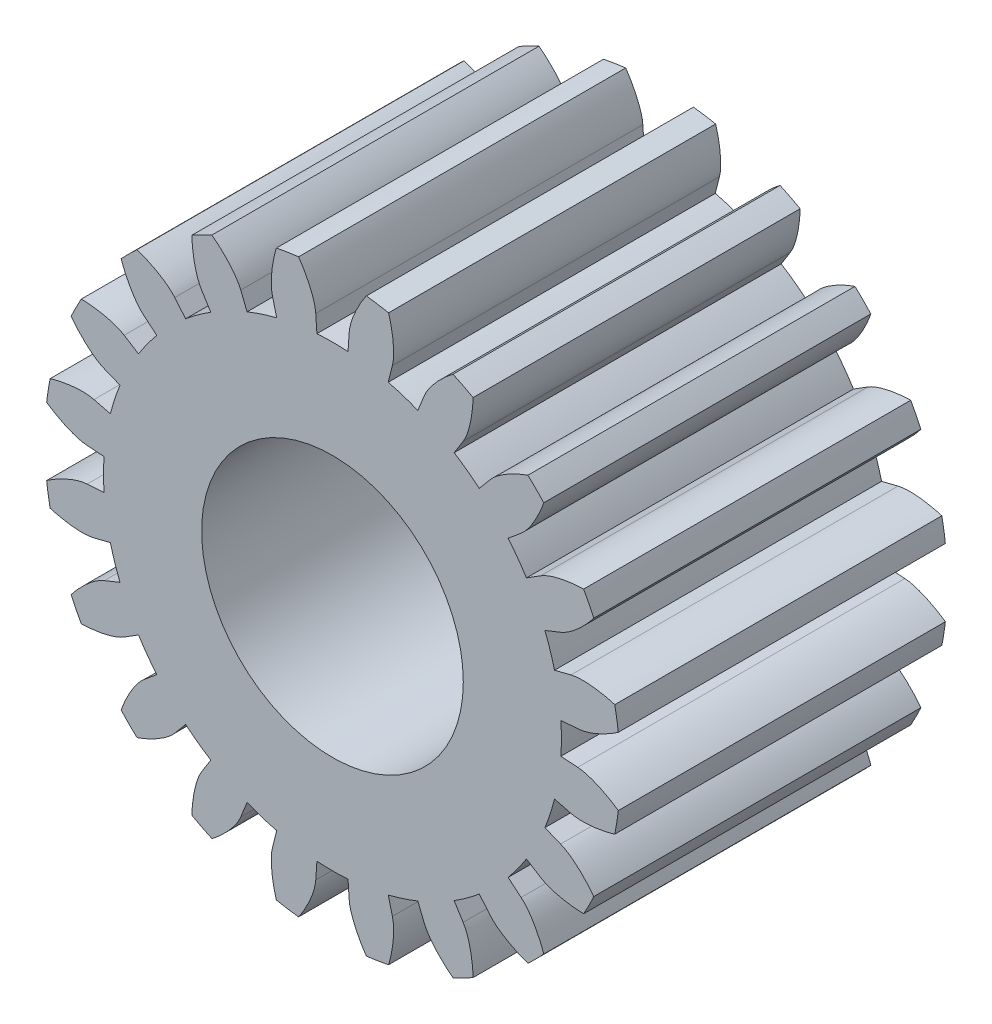
SolidWorks part; units mm, degrees
ref_plane "前视基准面" through (0, 0, 0) normal (0, 0, 1) x (1, 0, 0)
ref_plane "上视基准面" through (0, 0, 0) normal (0, 1, 0) x (1, 0, 0)
ref_plane "右视基准面" through (0, 0, 0) normal (1, 0, 0) x (0, 0, -1)
other "Configuration Table"
sketch "草图1" plane through (0, 0, 0) normal (0, 0, 1) x (1, 0, 0)
  line L0 (0, 0) -> (2, 0) construction
  line L1 (0, 0) -> (1.9938, 0.1569) construction
  line L2 (0, 0) -> (1.875, 0.1277)
  line L3 (1.9938, 0.1569) -> (1.9938, -0.1569) construction
  line L4 (0, 0) -> (1.875, -0.1277)
  circle A0 centre (0, 0) radius 2.2
  circle A1 centre (0, 0) radius 2 construction
  circle A2 centre (0, 0) radius 1.75
  circle A3 centre (0, 0) radius 1.8794 construction
  circle A4 centre (0, 0) radius 1
  spline S0 degree 4 poles (1.875, 0.1277) (1.8893, 0.1287) (1.929, 0.1344) (2.0025, 0.157) (2.1154, 0.2097) (2.2496, 0.2999) (2.4038, 0.439) (2.558, 0.6275) (2.6959, 0.8566) (2.809, 1.1216) (2.8885, 1.3983) (2.9362, 1.6822) (2.9548, 1.9837) (2.9388, 2.3574) (2.8628, 2.7975) (2.7005, 3.2908) (2.438, 3.8043) (2.1043, 4.2744) (1.7108, 4.6951) (1.2662, 5.062) (0.7817, 5.3723) (0.2626, 5.6242) (-0.2099, 5.7928) (-0.6312, 5.9005) (-0.9788, 5.9657) (-1.275, 6.0034) (-1.5146, 6.0246) (-1.7994, 6.0339) (-1.9848, 6.0333) (-2.2485, 6.0248) (-2.4456, 6.0069) (-2.6444, 5.9868) (-2.7432, 5.9706) (-2.8075, 5.9617) knots 0 0 0 0 0 0.005604 0.015718 0.02996 0.048734 0.068727 0.096889 0.125051 0.153212 0.181374 0.209535 0.237696 0.271429 0.327752 0.384075 0.440398 0.496721 0.553044 0.609367 0.66569 0.722013 0.778336 0.806497 0.834659 0.86282 0.890982 0.909091 0.931818 0.954545 0.977273 1 1 1 1 1 construction
  spline S1 degree 4 poles (1.875, 0.1277) (1.8893, 0.1287) (1.929, 0.1344) (2.0025, 0.157) (2.1154, 0.2097) (2.2496, 0.2999) (2.4038, 0.439) (2.558, 0.6275) (2.6959, 0.8566) (2.809, 1.1216) (2.8885, 1.3983) (2.9362, 1.6822) (2.9548, 1.9837) (2.9388, 2.3574) (2.8628, 2.7975) (2.7005, 3.2908) (2.438, 3.8043) (2.1043, 4.2744) (1.7108, 4.6951) (1.2662, 5.062) (0.7817, 5.3723) (0.2626, 5.6242) (-0.2099, 5.7928) (-0.6312, 5.9005) (-0.9788, 5.9657) (-1.275, 6.0034) (-1.5146, 6.0246) (-1.7328, 6.0317) (-1.8402, 6.033) (-1.8822, 6.033) knots 0 0 0 0 0 0.005604 0.015718 0.02996 0.048734 0.068727 0.096889 0.125051 0.153212 0.181374 0.209535 0.237696 0.271429 0.327752 0.384075 0.440398 0.496721 0.553044 0.609367 0.66569 0.722013 0.778336 0.806497 0.834659 0.86282 0.890982 0.909091 0.909091 0.909091 0.909091 0.909091
  spline S2 degree 4 poles (1.875, -0.1277) (1.8893, -0.1287) (1.929, -0.1344) (2.0025, -0.157) (2.1154, -0.2097) (2.2496, -0.2999) (2.4038, -0.439) (2.558, -0.6275) (2.6959, -0.8566) (2.809, -1.1216) (2.8885, -1.3983) (2.9362, -1.6822) (2.9548, -1.9837) (2.9388, -2.3574) (2.8628, -2.7975) (2.7005, -3.2908) (2.438, -3.8043) (2.1043, -4.2744) (1.7108, -4.6951) (1.2662, -5.062) (0.7817, -5.3723) (0.2626, -5.6242) (-0.2099, -5.7928) (-0.6312, -5.9005) (-0.9788, -5.9657) (-1.275, -6.0034) (-1.5146, -6.0246) (-1.7994, -6.0339) (-1.9848, -6.0333) (-2.2485, -6.0248) (-2.4456, -6.0069) (-2.6444, -5.9868) (-2.7432, -5.9706) (-2.8075, -5.9617) knots 0 0 0 0 0 0.005604 0.015718 0.02996 0.048734 0.068727 0.096889 0.125051 0.153212 0.181374 0.209535 0.237696 0.271429 0.327752 0.384075 0.440398 0.496721 0.553044 0.609367 0.66569 0.722013 0.778336 0.806497 0.834659 0.86282 0.890982 0.909091 0.931818 0.954545 0.977273 1 1 1 1 1 construction
  spline S3 degree 4 poles (1.875, -0.1277) (1.8893, -0.1287) (1.929, -0.1344) (2.0025, -0.157) (2.1154, -0.2097) (2.2496, -0.2999) (2.4038, -0.439) (2.558, -0.6275) (2.6959, -0.8566) (2.809, -1.1216) (2.8885, -1.3983) (2.9362, -1.6822) (2.9548, -1.9837) (2.9388, -2.3574) (2.8628, -2.7975) (2.7005, -3.2908) (2.438, -3.8043) (2.1043, -4.2744) (1.7108, -4.6951) (1.2662, -5.062) (0.7817, -5.3723) (0.2626, -5.6242) (-0.2099, -5.7928) (-0.6312, -5.9005) (-0.9788, -5.9657) (-1.275, -6.0034) (-1.5146, -6.0246) (-1.7328, -6.0317) (-1.8402, -6.033) (-1.8822, -6.033) knots 0 0 0 0 0 0.005604 0.015718 0.02996 0.048734 0.068727 0.096889 0.125051 0.153212 0.181374 0.209535 0.237696 0.271429 0.327752 0.384075 0.440398 0.496721 0.553044 0.609367 0.66569 0.722013 0.778336 0.806497 0.834659 0.86282 0.890982 0.909091 0.909091 0.909091 0.909091 0.909091
  point P15 (1.9938, 0)
  dimension "齿顶圆直径" = 4.4
  dimension "分度圆直径" = 4
  dimension "齿根圆直径" = 3.5
  dimension "基圆直径" = 3.7588
  dimension "内孔直径" = 2
  dimension "渐近线镜像线夹角" = 4.5
extrude "凸台-拉伸1" add sketch "草图1" along normal blind 2.5 contours A0 | A4
extrude "切除-拉伸1" cut sketch "草图1<3>" along normal through all contours A2 S3 A0 S1 region at (2.0041, 0, 0)
sketch "草图1<3>" plane through (0, 0, 0) normal (0, 0, 1) x (1, 0, 0) same geometry as "草图1"
pattern_circular "阵列(圆周)1" count 20 every 18 about axis through (0, 0, 2.5) along (0, 0, 1) of "切除-拉伸1"
equation "\"m\"= 0.2'模数"
equation "\"z\" = 20'齿数"
equation "\"a\"= 20度'压力角"
equation "\"d\"= \"m\" * \"z\"'分度圆直径"
equation "\"da\"= ( \"z\" + 2 ) * \"m\"'齿顶圆直径"
equation "\"df\"= ( \"z\" - 2.5 ) * \"m\"'齿根圆直径"
equation "\"s\"= 0.5 * PI * \"m\"'分度圆齿厚"
equation "\"r\"= 0.38 * \"m\"'齿根圆角"
equation "\"B\"= 0.3 * \"d\"'齿厚"
equation "\"db\"= \"m\" * \"z\" * cos ( \"a\" )'基圆直径"
equation "\"rb\"= \"db\" / 2'基圆半径"
equation "\"齿顶圆直径@草图1\"= \"da\""
equation "\"分度圆直径@草图1\"= \"d\""
equation "\"齿根圆直径@草图1\"= \"df\""
equation "\"基圆直径@草图1\"= \"db\""
equation "\"渐近线镜像线夹角@草图1\"= 360 / 4 / \"z\""
equation "\"h\" = 2.5'齿轮厚度"
equation "\"ir\"= 2'内孔直径"
equation "\"内孔直径@草图1\"= \"ir\""
equation "\"齿轮厚@凸台-拉伸1\"= \"h\""
equation "\"齿轮夹角@阵列(圆周)1\"= 360 / \"z\""
equation "\"齿数@阵列(圆周)1\"= \"z\""
